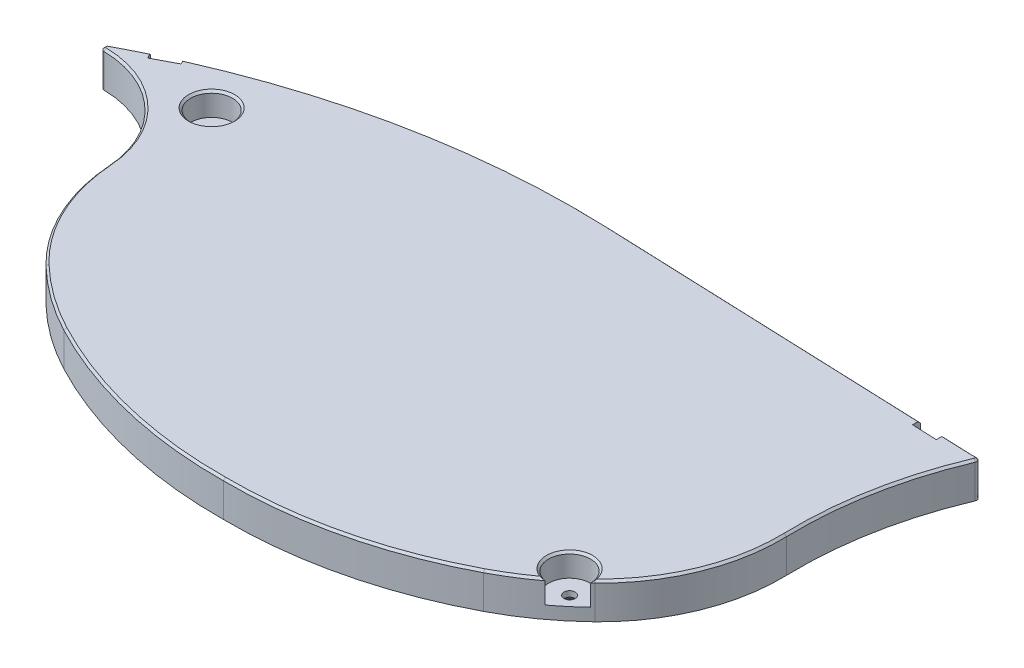
SolidWorks part; units mm, degrees
ref_plane "Front Plane" through (0, 0, 0) normal (0, 0, 1) x (1, 0, 0)
ref_plane "Top Plane" through (0, 0, 0) normal (0, 1, 0) x (1, 0, 0)
ref_plane "Right Plane" through (0, 0, 0) normal (1, 0, 0) x (0, 0, -1)
sketch "Main_line" plane through (0, 0, 0) normal (0, 1, 0) x (1, 0, 0)
  line L7 (125.3421, 60.9054) -> (34.6967, 64.397)
  line L8 (125.3421, 60.9054) -> (34.6967, 64.397) construction
  circle A36 centre (101.1451, -11.297) radius 1.35 construction
  circle A37 centre (-36.8676, 41.2561) radius 1.35 construction
  circle A38 centre (-36.8676, 41.2561) radius 1.35 construction
  arc A101 (125.3421, 60.9054) -> (126.2253, 60.9272) centre (125.6116, 67.9003) ccw
  arc A102 (34.6967, 64.397) -> (-62.1252, 42.3407) centre (27.3316, -126.8131) ccw
  arc A103 (-62.1252, 42.3407) -> (-61.8734, 40.3786) centre (-61.8533, 41.3784) ccw
  arc A104 (-37.8008, 17.4859) -> (-61.8734, 40.3786) centre (-62.3702, 15.7532) ccw
  arc A105 (-37.8008, 17.4859) -> (-24.5516, -10.8946) centre (5.8076, 20.5613) ccw
  arc A106 (-24.5516, -10.8946) -> (-9.0652, -22.0786) centre (22.2519, 37.5995) ccw
  arc A107 (-9.0652, -22.0786) -> (41.1324, -34.1453) centre (39.9254, 71.2784) ccw
  arc A108 (41.1324, -34.1453) -> (91.33, -22.0786) centre (42.3395, 71.2784) ccw
  arc A109 (91.33, -22.0786) -> (106.8164, -10.8946) centre (60.013, 37.5995) ccw
  arc A110 (106.8164, -10.8946) -> (120.1306, 21.7195) centre (76.517, 20.4993) ccw
  arc A111 (127.2343, 59.5423) -> (120.1306, 21.7195) centre (210.8595, 24.2577) ccw
  arc A112 (127.2343, 59.5423) -> (126.2253, 60.9272) centre (126.3129, 59.9311) ccw
  arc A113 (125.3421, 60.9054) -> (126.2253, 60.9272) centre (125.6116, 67.9003) ccw construction
  arc A114 (34.6967, 64.397) -> (-62.1252, 42.3407) centre (27.3316, -126.8131) ccw construction
  arc A115 (-62.1252, 42.3407) -> (-61.8734, 40.3786) centre (-61.8533, 41.3784) ccw construction
  arc A116 (-37.8008, 17.4859) -> (-61.8734, 40.3786) centre (-62.3702, 15.7532) ccw construction
  arc A117 (-37.8008, 17.4859) -> (-24.5516, -10.8946) centre (5.8076, 20.5613) ccw construction
  arc A118 (-24.5516, -10.8946) -> (-9.0652, -22.0786) centre (22.2519, 37.5995) ccw construction
  arc A119 (-9.0652, -22.0786) -> (41.1324, -34.1453) centre (39.9254, 71.2784) ccw construction
  arc A120 (41.1324, -34.1453) -> (91.33, -22.0786) centre (42.3395, 71.2784) ccw construction
  arc A121 (91.33, -22.0786) -> (106.8164, -10.8946) centre (60.013, 37.5995) ccw construction
  arc A122 (106.8164, -10.8946) -> (120.1306, 21.7195) centre (76.517, 20.4993) ccw construction
  arc A123 (127.2343, 59.5423) -> (120.1306, 21.7195) centre (210.8595, 24.2577) ccw construction
  arc A124 (127.2343, 59.5423) -> (126.2253, 60.9272) centre (126.3129, 59.9311) ccw construction
  dimension "D1" = 0
sketch "Sketch1" plane through (0, 0, 0) normal (0, 1, 0) x (1, 0, 0)
  line L0 (112.386, 61.2043) -> (112.3167, 59.4057) construction
  line L1 (112.3167, 59.4057) -> (118.2284, 59.178) construction
  line L2 (125.3344, 60.7056) -> (34.689, 64.1971)
  line L3 (125.3344, 60.7056) -> (34.689, 64.1971)
  line L4 (118.2284, 59.178) -> (118.2977, 60.9766) construction
  line L5 (118.3054, 61.1765) -> (118.2284, 59.178) construction
  line L6 (112.3167, 59.4057) -> (112.3937, 61.4042) construction
  line L7 (-55.6078, 45.4079) -> (-54.8282, 43.9308) construction
  line L8 (-54.8282, 43.9308) -> (-49.5962, 46.6924) construction
  line L9 (-49.5962, 46.6924) -> (-50.2311, 47.8954) construction
  line L10 (-49.5962, 46.6924) -> (-50.3247, 48.0727) construction
  line L14 (-55.7012, 45.5849) -> (-54.8282, 43.9308) construction
  circle A90 centre (-36.8676, 41.2561) radius 1.35
  circle A91 centre (101.1451, -11.297) radius 1.35
  circle A92 centre (-36.8676, 41.2561) radius 1.35 construction
  arc A102 (125.3344, 60.7056) -> (126.2428, 60.728) centre (125.6116, 67.9003) ccw
  arc A103 (127.05, 59.6201) -> (126.2428, 60.728) centre (126.3129, 59.9311) ccw
  arc A104 (127.05, 59.6201) -> (119.9307, 21.7139) centre (210.8595, 24.2577) ccw
  arc A105 (106.6775, -10.7507) -> (119.9307, 21.7139) centre (76.517, 20.4993) ccw
  arc A106 (91.2371, -21.9015) -> (106.6775, -10.7507) centre (60.013, 37.5995) ccw
  arc A107 (41.1324, -33.9453) -> (91.2371, -21.9015) centre (42.3395, 71.2784) ccw
  arc A108 (-8.9722, -21.9015) -> (41.1324, -33.9453) centre (39.9254, 71.2784) ccw
  arc A109 (-24.4127, -10.7507) -> (-8.9722, -21.9015) centre (22.2519, 37.5995) ccw
  arc A110 (-37.6013, 17.4999) -> (-24.4127, -10.7507) centre (5.8076, 20.5613) ccw
  arc A111 (-37.6013, 17.4999) -> (-61.8694, 40.5786) centre (-62.3702, 15.7532) ccw
  arc A112 (-62.0515, 42.1534) -> (-61.8694, 40.5786) centre (-61.8533, 41.3784) ccw
  arc A113 (34.689, 64.1971) -> (-62.0515, 42.1534) centre (27.3316, -126.8131) ccw
  arc A114 (125.3344, 60.7056) -> (126.2428, 60.728) centre (125.6116, 67.9003) ccw
  arc A115 (127.05, 59.6201) -> (126.2428, 60.728) centre (126.3129, 59.9311) ccw
  arc A116 (127.05, 59.6201) -> (119.9307, 21.7139) centre (210.8595, 24.2577) ccw
  arc A117 (106.6775, -10.7507) -> (119.9307, 21.7139) centre (76.517, 20.4993) ccw
  arc A118 (91.2371, -21.9015) -> (106.6775, -10.7507) centre (60.013, 37.5995) ccw
  arc A119 (41.1324, -33.9453) -> (91.2371, -21.9015) centre (42.3395, 71.2784) ccw
  arc A120 (-8.9722, -21.9015) -> (41.1324, -33.9453) centre (39.9254, 71.2784) ccw
  arc A121 (-24.4127, -10.7507) -> (-8.9722, -21.9015) centre (22.2519, 37.5995) ccw
  arc A122 (-37.6013, 17.4999) -> (-24.4127, -10.7507) centre (5.8076, 20.5613) ccw
  arc A123 (-37.6013, 17.4999) -> (-61.8694, 40.5786) centre (-62.3702, 15.7532) ccw
  arc A124 (-62.0515, 42.1534) -> (-61.8694, 40.5786) centre (-61.8533, 41.3784) ccw
  arc A125 (34.689, 64.1971) -> (-62.0515, 42.1534) centre (27.3316, -126.8131) ccw
  dimension "D1" = 0.2
extrude "Boss-Extrude1" add sketch "Sketch1" along normal blind 3
sketch "Sketch2" plane through (0, 0, 0) normal (0, -1, 0) x (1, 0, 0)
  circle A0 centre (-36.8676, -41.2561) radius 2.5
  circle A1 centre (101.1451, 11.297) radius 2.5
  dimension "D1" = 5
extrude "Cut-Extrude1" cut sketch "Sketch2" against normal blind 1.7
chamfer "Chamfer1" distance 1.2 angle 45 2 edges at (101.1451, 1.7, 8.797) (-36.8676, 1.7, -43.7561)
sketch "Sketch3" plane through (0, 3, 0) normal (0, 1, 0) x (1, 0, 0)
  line L14 (125.3344, 60.7056) -> (34.689, 64.1971)
  line L15 (125.3344, 60.7056) -> (34.689, 64.1971)
  circle A0 centre (-36.8676, 41.2561) radius 5
  arc A1 (106.1449, -11.2591) -> (100.2517, -16.2165) centre (101.1451, -11.297) ccw
  arc A80 (106.1449, -11.2591) -> (106.6775, -10.7507) centre (60.013, 37.5995) ccw
  arc A92 (34.689, 64.1971) -> (-62.0515, 42.1534) centre (27.3316, -126.8131) ccw
  arc A93 (-62.0515, 42.1534) -> (-61.8694, 40.5786) centre (-61.8533, 41.3784) ccw
  arc A94 (-37.6013, 17.4999) -> (-61.8694, 40.5786) centre (-62.3702, 15.7532) ccw
  arc A95 (-37.6013, 17.4999) -> (-24.4127, -10.7507) centre (5.8076, 20.5613) ccw
  arc A96 (-24.4127, -10.7507) -> (-8.9722, -21.9015) centre (22.2519, 37.5995) ccw
  arc A97 (-8.9722, -21.9015) -> (41.1324, -33.9453) centre (39.9254, 71.2784) ccw
  arc A98 (41.1324, -33.9453) -> (91.2371, -21.9015) centre (42.3395, 71.2784) ccw
  arc A99 (91.2371, -21.9015) -> (106.6775, -10.7507) centre (60.013, 37.5995) ccw
  arc A100 (106.6775, -10.7507) -> (119.9307, 21.7139) centre (76.517, 20.4993) ccw
  arc A101 (127.05, 59.6201) -> (119.9307, 21.7139) centre (210.8595, 24.2577) ccw
  arc A102 (127.05, 59.6201) -> (126.2428, 60.728) centre (126.3129, 59.9311) ccw
  arc A103 (125.3344, 60.7056) -> (126.2428, 60.728) centre (125.6116, 67.9003) ccw
  arc A104 (34.689, 64.1971) -> (-62.0515, 42.1534) centre (27.3316, -126.8131) ccw
  arc A105 (-62.0515, 42.1534) -> (-61.8694, 40.5786) centre (-61.8533, 41.3784) ccw
  arc A106 (-37.6013, 17.4999) -> (-61.8694, 40.5786) centre (-62.3702, 15.7532) ccw
  arc A107 (-37.6013, 17.4999) -> (-24.4127, -10.7507) centre (5.8076, 20.5613) ccw
  arc A108 (-24.4127, -10.7507) -> (-8.9722, -21.9015) centre (22.2519, 37.5995) ccw
  arc A109 (-8.9722, -21.9015) -> (41.1324, -33.9453) centre (39.9254, 71.2784) ccw
  arc A110 (41.1324, -33.9453) -> (91.2371, -21.9015) centre (42.3395, 71.2784) ccw
  arc A111 (91.2371, -21.9015) -> (100.2517, -16.2165) centre (60.013, 37.5995) ccw
  arc A112 (106.6775, -10.7507) -> (119.9307, 21.7139) centre (76.517, 20.4993) ccw
  arc A113 (127.05, 59.6201) -> (119.9307, 21.7139) centre (210.8595, 24.2577) ccw
  arc A114 (127.05, 59.6201) -> (126.2428, 60.728) centre (126.3129, 59.9311) ccw
  arc A115 (125.3344, 60.7056) -> (126.2428, 60.728) centre (125.6116, 67.9003) ccw
  dimension "D1" = 10
  dimension "D2" = 0
extrude "Boss-Extrude2" add sketch "Sketch3" along normal blind 5.5
chamfer "Chamfer2" distance 0.5 angle 45 2 edges at (97.9264, 8.5, 7.4707) (-36.8676, 8.5, -36.2561)
chamfer "Chamfer3" distance 0.5 angle 45 14 edges at (95.5776, 8.5, 19.4135) (66.9334, 8.5, 31.0379) (15.3315, 8.5, 31.0379) (-17.0895, 8.5, 16.8759) (-33.6238, 8.5, -2.153) (-45.2589, 8.5, -33.7464) (-62.648, 8.5, -41.2865) (106.6502, 8.5, 10.777) (116.7262, 8.5, -4.0846) (121.4582, 8.5, -41.0486) (126.9595, 8.5, -60.4022) (125.789, 8.5, -60.7024) (-15.1364, 8.5, -59.5615) (80.0117, 8.5, -62.4514)
sketch "Sketch4" plane through (0, 8.5, 0) normal (0, 1, 0) x (1, 0, 0)
  line L0 (-55.6078, 45.4079) -> (-54.8282, 43.9308)
  line L1 (-54.8282, 43.9308) -> (-49.5962, 46.6924)
  line L2 (-49.5962, 46.6924) -> (-50.2311, 47.8954)
  line L3 (-50.2311, 47.8954) -> (-50.8426, 49.0539)
  line L4 (-50.8426, 49.0539) -> (-56.0746, 46.2923)
  line L5 (-56.0746, 46.2923) -> (-55.6078, 45.4079)
  line L6 (112.386, 61.2043) -> (112.3167, 59.4057)
  line L7 (112.3167, 59.4057) -> (118.2284, 59.178)
  line L8 (118.2284, 59.178) -> (118.2977, 60.9766)
  line L9 (118.2977, 60.9766) -> (112.386, 61.2043)
  dimension "D1" = 1
extrude "Cut-Extrude2" cut sketch "Sketch4" against normal blind 5
